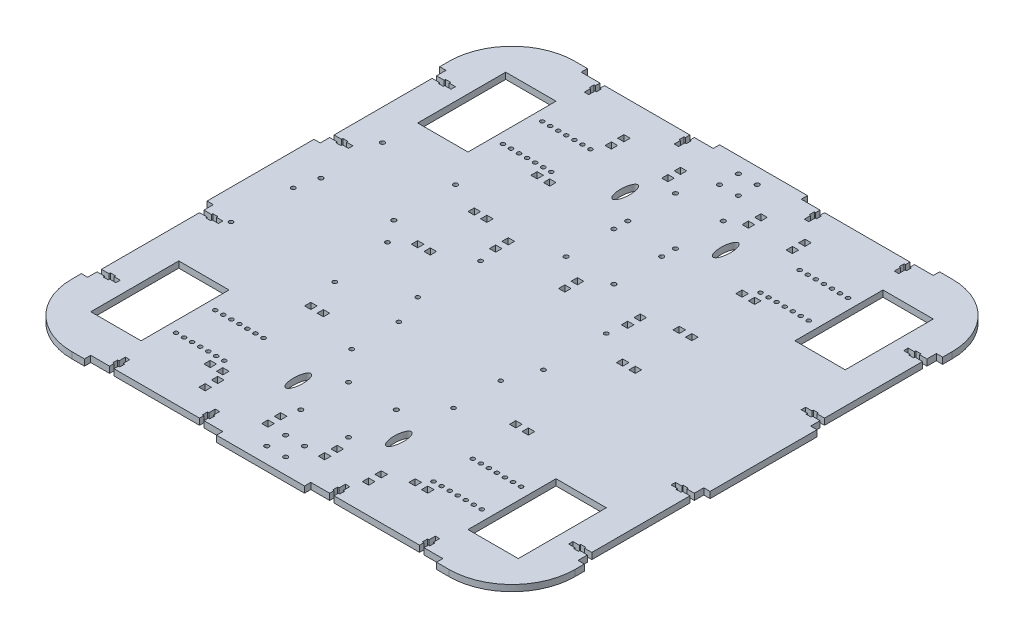
SolidWorks part; units mm, degrees
ref_plane "Front Plane" through (0, 0, 0) normal (0, 0, 1) x (1, 0, 0)
ref_plane "Top Plane" through (0, 0, 0) normal (0, 1, 0) x (1, 0, 0)
ref_plane "Right Plane" through (0, 0, 0) normal (1, 0, 0) x (0, 0, -1)
sketch "Sketch1" plane through (0, 0, 0) normal (0, 1, 0) x (1, 0, 0)
  line L0 (0, -1000) -> (0, 49000) construction
  line L1 (-170, 165) -> (-130, 165)
  line L2 (-170, 165) -> (-170, 95)
  line L3 (-170, 95) -> (-130, 95)
  line L4 (-130, 165) -> (-130, 95)
  line L5 (170, 95) -> (130, 95)
  line L6 (130, 165) -> (130, 95)
  line L7 (170, 165) -> (130, 165)
  line L8 (170, 165) -> (170, 95)
  line L9 (-1000, 0) -> (49000, 0) construction
  line L10 (-10, 190) -> (10, 190)
  line L11 (-10, 190) -> (-10, 170)
  line L12 (-10, 170) -> (10, 170)
  line L13 (10, 190) -> (10, 170)
  line L14 (-1010, 180) -> (48990, 180) construction
  line L15 (-1010, -180) -> (48990, -180) construction
  line L16 (0, 1000) -> (0, -49000) construction
  line L17 (-10, -170) -> (10, -170)
  line L18 (10, -190) -> (10, -170)
  line L19 (-10, -190) -> (10, -190)
  line L20 (-10, -190) -> (-10, -170)
  line L21 (170, -165) -> (170, -95)
  line L22 (-200, 200) -> (200, 200)
  line L23 (-200, 200) -> (-200, -200)
  line L24 (-200, -200) -> (200, -200)
  line L25 (200, 200) -> (200, -200)
  line L26 (170, -165) -> (130, -165)
  line L27 (130, -165) -> (130, -95)
  line L28 (170, -95) -> (130, -95)
  line L29 (-170, -95) -> (-130, -95)
  line L30 (-130, -165) -> (-130, -95)
  line L31 (-170, -165) -> (-130, -165)
  line L32 (-170, -165) -> (-170, -95)
  circle A0 centre (0, 0) radius 200 construction
  circle A1 centre (-7.5, 187.5) radius 1.75
  circle A2 centre (7.5, 187.5) radius 1.75
  circle A3 centre (7.5, 172.5) radius 1.75
  circle A4 centre (-7.5, 172.5) radius 1.75
  circle A5 centre (7.5, -187.5) radius 1.75
  circle A6 centre (-7.5, -187.5) radius 1.75
  circle A7 centre (-7.5, -172.5) radius 1.75
  circle A8 centre (7.5, -172.5) radius 1.75
  point P8 (-150, 165)
  point P19 (0, 190)
  point P22 (-10, 180)
  dimension "D1" = 400
  dimension "D7" = 3.5
  dimension "D2" = 40
  dimension "D3" = 70
  dimension "D4" = 150
  dimension "D5" = 20
  dimension "D6" = 180
  dimension "D8" = 2.5
  dimension "D9" = 2.5
  dimension "D10" = 35
extrude "Boss-Extrude2" add sketch "Sketch1" along normal blind 5 contours L25 L22 L23 L24 L1 L4 L3 L2 L7 L8 L5 L6 L10 L13 L12 L11 L19 L20 L17 L18 | L20 L19 L18 L17 A6 A5 A7 A8 | L13 L10 L11 L12 A2 A1 A3 A4 region at (0, 0, -180) region at (0, 0, 180) region at (0, 0, 0)
fillet "Fillet1" radius 50 4 edges at (200, 2.5, -200) (200, 2.5, 200) (-200, 2.5, 200) (-200, 2.5, -200)
sketch "Sketch2" plane through (0, 5, 0) normal (0, 1, 0) x (1, 0, 0)
  line L0 (-1094.0419, 130) -> (48905.9581, 130) construction
  line L1 (-130, 148.8) -> (-78.5, 148.8) construction
  line L2 (-130, 148.8) -> (-130, 111.2) construction
  line L3 (-130, 111.2) -> (-78.5, 111.2) construction
  line L4 (-78.5, 148.8) -> (-78.5, 111.2) construction
  line L5 (-130, 165) -> (-130, 95) construction
  line L6 (-170, 165) -> (-170, 95) construction
  line L7 (0, -1000) -> (0, 49000) construction
  line L8 (130, 111.2) -> (78.5, 111.2) construction
  line L9 (78.5, 148.8) -> (78.5, 111.2) construction
  line L10 (130, 148.8) -> (78.5, 148.8) construction
  line L11 (130, 148.8) -> (130, 111.2) construction
  line L12 (-1000, 0) -> (49000, 0) construction
  line L13 (130, -148.8) -> (130, -111.2) construction
  line L14 (130, -148.8) -> (78.5, -148.8) construction
  line L15 (78.5, -148.8) -> (78.5, -111.2) construction
  line L16 (130, -111.2) -> (78.5, -111.2) construction
  line L17 (-78.5, -148.8) -> (-78.5, -111.2) construction
  line L18 (-130, -111.2) -> (-78.5, -111.2) construction
  line L19 (-130, -148.8) -> (-130, -111.2) construction
  line L20 (-130, -148.8) -> (-78.5, -148.8) construction
  line L21 (-1094.0419, -130) -> (48905.9581, -130) construction
  circle A0 centre (-121.6, 145.6) radius 1.6
  circle A1 centre (-115.2, 145.6) radius 1.6
  circle A2 centre (-108.8, 145.6) radius 1.6
  circle A3 centre (-102.4, 145.6) radius 1.6
  circle A4 centre (-96, 145.6) radius 1.6
  circle A5 centre (-89.6, 145.6) radius 1.6
  circle A6 centre (-83.2, 145.6) radius 1.6
  circle A7 centre (-83.2, 114.4) radius 1.6
  circle A8 centre (-89.6, 114.4) radius 1.6
  circle A9 centre (-96, 114.4) radius 1.6
  circle A10 centre (-102.4, 114.4) radius 1.6
  circle A11 centre (-108.8, 114.4) radius 1.6
  circle A12 centre (-115.2, 114.4) radius 1.6
  circle A13 centre (-121.6, 114.4) radius 1.6
  circle A14 centre (83.2, 114.4) radius 1.6
  circle A15 centre (89.6, 114.4) radius 1.6
  circle A16 centre (96, 114.4) radius 1.6
  circle A17 centre (102.4, 114.4) radius 1.6
  circle A18 centre (108.8, 114.4) radius 1.6
  circle A19 centre (115.2, 114.4) radius 1.6
  circle A20 centre (121.6, 114.4) radius 1.6
  circle A21 centre (83.2, 145.6) radius 1.6
  circle A22 centre (89.6, 145.6) radius 1.6
  circle A23 centre (96, 145.6) radius 1.6
  circle A24 centre (102.4, 145.6) radius 1.6
  circle A25 centre (108.8, 145.6) radius 1.6
  circle A26 centre (115.2, 145.6) radius 1.6
  circle A27 centre (121.6, 145.6) radius 1.6
  circle A28 centre (121.6, -145.6) radius 1.6
  circle A29 centre (115.2, -145.6) radius 1.6
  circle A30 centre (108.8, -145.6) radius 1.6
  circle A31 centre (102.4, -145.6) radius 1.6
  circle A32 centre (96, -145.6) radius 1.6
  circle A33 centre (89.6, -145.6) radius 1.6
  circle A34 centre (83.2, -145.6) radius 1.6
  circle A35 centre (121.6, -114.4) radius 1.6
  circle A36 centre (115.2, -114.4) radius 1.6
  circle A37 centre (108.8, -114.4) radius 1.6
  circle A38 centre (102.4, -114.4) radius 1.6
  circle A39 centre (96, -114.4) radius 1.6
  circle A40 centre (89.6, -114.4) radius 1.6
  circle A41 centre (83.2, -114.4) radius 1.6
  circle A42 centre (-121.6, -114.4) radius 1.6
  circle A43 centre (-115.2, -114.4) radius 1.6
  circle A44 centre (-108.8, -114.4) radius 1.6
  circle A45 centre (-102.4, -114.4) radius 1.6
  circle A46 centre (-96, -114.4) radius 1.6
  circle A47 centre (-89.6, -114.4) radius 1.6
  circle A48 centre (-83.2, -114.4) radius 1.6
  circle A49 centre (-83.2, -145.6) radius 1.6
  circle A50 centre (-89.6, -145.6) radius 1.6
  circle A51 centre (-96, -145.6) radius 1.6
  circle A52 centre (-102.4, -145.6) radius 1.6
  circle A53 centre (-108.8, -145.6) radius 1.6
  circle A54 centre (-115.2, -145.6) radius 1.6
  circle A55 centre (-121.6, -145.6) radius 1.6
  point P9 (-130, 130)
  point P40 (-170, 130)
  dimension "D3" = 3.2
  dimension "D7" = 6.4
  dimension "D5" = 8.4
  dimension "D1" = 37.6
  dimension "D2" = 4.7
  dimension "D4" = 31.2
  dimension "D6" = 7
extrude "Cut-Extrude1" cut sketch "Sketch2" against normal blind 5
sketch "Sketch3" plane through (0, 5, 0) normal (0, 1, 0) x (1, 0, 0)
  line L0 (-150, -200) -> (150, -200) construction
  line L1 (-190, 3.34) -> (-88.4, 3.34) construction
  line L2 (-190, 3.34) -> (-190, -50) construction
  line L3 (-190, -50) -> (-88.4, -50) construction
  line L4 (-88.4, 3.34) -> (-88.4, -50) construction
  line L5 (-200, 150) -> (-200, -150) construction
  circle A0 centre (-176.03, -47.46) radius 1.65
  circle A1 centre (-174.76, 0.8) radius 1.65
  circle A2 centre (-93.48, -47.46) radius 1.65
  circle A3 centre (-99.83, 0.8) radius 1.65
  dimension "D5" = 3.3
  dimension "D8" = 3.3
  dimension "D9" = 96.52
  dimension "D10" = 90.17
  dimension "D1" = 101.6
  dimension "D2" = 53.34
  dimension "D3" = 13.97
  dimension "D4" = 2.54
  dimension "D6" = 15.24
  dimension "D7" = 50.8
  dimension "D11" = 150
  dimension "D12" = 10
extrude "Cut-Extrude2" cut sketch "Sketch3" against normal blind 10 contours A1 | A2 | L2 L1 L4 L3 | A0 | A3 region at (-174.76, 5, -0.8) region at (-93.48, 5, 47.46)
sketch "Sketch4" plane through (0, 5, 0) normal (0, 1, 0) x (1, 0, 0)
  line L0 (-19, 149) -> (19, 149) construction
  line L1 (-1149.7342, 130) -> (48850.2658, 130) construction
  line L2 (-22, 152) -> (22, 152) construction
  line L3 (-22, 152) -> (-22, 108) construction
  line L4 (-22, 108) -> (22, 108) construction
  line L5 (22, 152) -> (22, 108) construction
  line L6 (-19, 111) -> (19, 111) construction
  line L7 (-19, 100) -> (19, 100) construction
  line L8 (-1231.3219, 81) -> (48768.6781, 81) construction
  line L9 (-22, 103) -> (22, 103) construction
  line L10 (-22, 103) -> (-22, 59) construction
  line L11 (-22, 59) -> (22, 59) construction
  line L12 (22, 103) -> (22, 59) construction
  line L13 (-19, 62) -> (19, 62) construction
  line L14 (-19, -149) -> (19, -149) construction
  line L15 (-22, -152) -> (22, -152) construction
  line L16 (-130, 165) -> (-130, 95) construction
  line L17 (-150, 200) -> (150, 200) construction
  line L18 (22, -108) -> (22, -152) construction
  line L19 (-22, -108) -> (-22, -152) construction
  line L20 (-19, -111) -> (19, -111) construction
  line L21 (-22, -108) -> (22, -108) construction
  line L22 (-1022, -130) -> (48978, -130) construction
  line L23 (-130, -165) -> (-130, -95) construction
  circle A0 centre (-19, 149) radius 1.75
  circle A1 centre (19, 149) radius 1.75
  circle A2 centre (19, 111) radius 1.75
  circle A3 centre (-19, 111) radius 1.75
  circle A4 centre (-19, 100) radius 1.75
  circle A5 centre (19, 100) radius 1.75
  circle A6 centre (19, 62) radius 1.75
  circle A7 centre (-19, 62) radius 1.75
  circle A8 centre (-19, -149) radius 1.75
  circle A9 centre (19, -149) radius 1.75
  circle A10 centre (-19, -111) radius 1.75
  circle A11 centre (19, -111) radius 1.75
  point P9 (0, 149)
  point P10 (0, 152)
  point P14 (-22, 130)
  point P26 (0, 100)
  point P27 (0, 103)
  point P31 (-22, 81)
  point P38 (-130, 130)
  point P39 (0, 200)
  point P40 (0, 108)
  point P56 (-22, -130)
  point P58 (-130, -130)
  dimension "D1" = 3.5
  dimension "D5" = 3.5
  dimension "D2" = 38
  dimension "D3" = 44
  dimension "D4" = 38
  dimension "D6" = 38
  dimension "D7" = 44
  dimension "D8" = 38
  dimension "D9" = 5
  dimension "D10" = 2
extrude "Cut-Extrude3" cut sketch "Sketch4" against normal blind 10
sketch "Sketch5" plane through (0, 5, 0) normal (0, 1, 0) x (1, 0, 0)
  line L0 (-1136.3236, 43) -> (48863.6764, 43) construction
  line L1 (-174, 15) -> (-89, 15) construction
  line L2 (-174, 15) -> (-174, 71) construction
  line L3 (-174, 71) -> (-89, 71) construction
  line L4 (-89, 15) -> (-89, 71) construction
  line L5 (-180, 10) -> (-83, 10) construction
  line L6 (-180, 10) -> (-180, 76) construction
  line L7 (-180, 76) -> (-83, 76) construction
  line L8 (-83, 10) -> (-83, 76) construction
  line L9 (-200, 150) -> (-200, -150) construction
  line L10 (-150, -200) -> (150, -200) construction
  circle A0 centre (-170.5, 67.5) radius 1.75
  circle A1 centre (-112.5, 67.5) radius 1.75
  circle A2 centre (-112.5, 18.5) radius 1.75
  circle A3 centre (-170.5, 18.5) radius 1.75
  dimension "D4" = 3.5
  dimension "D5" = 3.5
  dimension "D1" = 56
  dimension "D2" = 85
  dimension "D3" = 58
  dimension "D6" = 3.5
  dimension "D7" = 49
  dimension "D8" = 3.5
  dimension "D9" = 5
  dimension "D10" = 5
  dimension "D11" = 6
  dimension "D12" = 6
  dimension "D13" = 20
  dimension "D14" = 210
extrude "Cut-Extrude4" cut sketch "Sketch5" against normal blind 10
sketch "Sketch6" plane through (0, 5, 0) normal (0, 1, 0) x (1, 0, 0)
  line L0 (-130, 165) -> (-130, 95) construction
  line L1 (0, -800) -> (0, 49200) construction
  line L2 (-150, 200) -> (150, 200) construction
  line L3 (-1200, 0) -> (48800, 0) construction
  line L4 (-200, 150) -> (-200, -150) construction
  ellipse E0 centre (-40, 130) end of major axis (-40, 140) minor radius 3.75
  ellipse E1 centre (40, 130) end of major axis (40, 140) minor radius 3.75
  ellipse E2 centre (40, -130) end of major axis (40, -140) minor radius 3.75
  ellipse E3 centre (-40, -130) end of major axis (-40, -140) minor radius 3.75
  point P13 (-130, 130)
  point P14 (-200, 0)
  point P26 (0, 200)
  dimension "D1" = 90
  dimension "D2" = 20
  dimension "D3" = 7.5
extrude "Cut-Extrude5" cut sketch "Sketch6" against normal blind 10
sketch "Sketch7" plane through (0, 5, 0) normal (0, 1, 0) x (1, 0, 0)
  line L0 (0, -1008.1082) -> (0, 48991.8918) construction
  line L1 (-53, 28) -> (53, 28) construction
  line L2 (-53, 28) -> (-53, -28) construction
  line L3 (-53, -28) -> (53, -28) construction
  line L4 (53, 28) -> (53, -28) construction
  line L5 (-53, 28) -> (-47, 28) construction
  line L6 (-53, 28) -> (-53, 22) construction
  line L7 (-53, 22) -> (-47, 22) construction
  line L8 (-47, 28) -> (-47, 22) construction
  line L9 (-1053, 0) -> (48947, 0) construction
  line L10 (-150, -200) -> (150, -200) construction
  line L11 (-200, 150) -> (-200, -150) construction
  circle A1 centre (-50, 25) radius 1.65
  circle A2 centre (50, 25) radius 1.65
  circle A3 centre (50, -25) radius 1.65
  circle A4 centre (-50, -25) radius 1.65
  point P10 (-50, 22)
  point P15 (-47, 25)
  point P16 (0, 28)
  point P17 (-53, 0)
  point P25 (0, -200)
  point P28 (-200, 0)
  dimension "D3" = 3.3
  dimension "D1" = 106
  dimension "D2" = 56
  dimension "D5" = 6
  dimension "D6" = 6
extrude "Cut-Extrude6" cut sketch "Sketch7" against normal blind 10
sketch "Sketch8" plane through (0, 5, 0) normal (0, 1, 0) x (1, 0, 0)
  line L0 (0, -1046.6714) -> (0, 48953.3286) construction
  line L1 (-43.5, -46.5) -> (43.5, -46.5) construction
  line L2 (-43.5, -46.5) -> (-43.5, -90) construction
  line L3 (-43.5, -90) -> (43.5, -90) construction
  line L4 (43.5, -46.5) -> (43.5, -90) construction
  line L5 (-43.5, -46.5) -> (-37.5, -46.5) construction
  line L6 (-43.5, -46.5) -> (-43.5, -52.5) construction
  line L7 (-43.5, -52.5) -> (-37.5, -52.5) construction
  line L8 (-37.5, -46.5) -> (-37.5, -52.5) construction
  line L9 (-1043.5, -68.25) -> (48956.5, -68.25) construction
  line L10 (37.5, -46.5) -> (37.5, -52.5) construction
  line L11 (43.5, -52.5) -> (37.5, -52.5) construction
  line L12 (-150, -200) -> (150, -200) construction
  circle A0 centre (-40.5, -49.5) radius 1.65
  circle A1 centre (40.5, -49.5) radius 1.65
  circle A2 centre (40.5, -87) radius 1.65
  circle A3 centre (-40.5, -87) radius 1.65
  point P10 (-40.5, -52.5)
  point P11 (-37.5, -49.5)
  point P15 (0, -46.5)
  point P17 (-43.5, -68.25)
  point P28 (0, -200)
  dimension "D3" = 3.3
  dimension "D1" = 87
  dimension "D2" = 6
  dimension "D4" = 43.5
  dimension "D5" = 110
extrude "Cut-Extrude7" cut sketch "Sketch8" against normal blind 5
sketch "Sketch10" plane through (0, 5, 0) normal (0, 1, 0) x (1, 0, 0)
  line L0 (-150, -200) -> (150, -200) construction
  line L1 (-125, -200) -> (-121.5, -200)
  line L2 (-125, -200) -> (-125, -191.5)
  line L3 (-125, -182.5) -> (-121.5, -182.5)
  line L4 (-121.5, -200) -> (-121.5, -191.5)
  line L6 (-121.5, -187.5) -> (-120.4, -187.5)
  line L7 (-126.1, -187.5) -> (-125, -187.5)
  line L8 (-126.1, -187.5) -> (-126.1, -191.5)
  line L9 (-126.1, -191.5) -> (-125, -191.5)
  line L10 (-120.4, -187.5) -> (-120.4, -191.5)
  line L11 (-121.5, -191.5) -> (-120.4, -191.5)
  line L12 (-125, -187.5) -> (-125, -182.5)
  line L13 (-121.5, -187.5) -> (-121.5, -182.5)
  line L14 (-125, -187.5) -> (-121.5, -187.5) construction
  line L15 (-121.5, -191.5) -> (-125, -191.5) construction
  line L16 (-53.5, -200) -> (-50, -200)
  line L17 (-50, -200) -> (-50, -191.5)
  line L18 (-50, -191.5) -> (-48.9, -191.5)
  line L19 (-48.9, -187.5) -> (-48.9, -191.5)
  line L20 (-50, -187.5) -> (-48.9, -187.5)
  line L21 (-50, -187.5) -> (-50, -182.5)
  line L22 (-53.5, -182.5) -> (-50, -182.5)
  line L23 (-53.5, -187.5) -> (-53.5, -182.5)
  line L24 (-54.6, -187.5) -> (-53.5, -187.5)
  line L25 (-54.6, -187.5) -> (-54.6, -191.5)
  line L26 (-54.6, -191.5) -> (-53.5, -191.5)
  line L27 (-53.5, -200) -> (-53.5, -191.5)
  line L28 (-50, -191.5) -> (-53.5, -191.5) construction
  line L29 (-53.5, -187.5) -> (-50, -187.5) construction
  line L30 (0, -1200) -> (0, 48800) construction
  line L31 (-200, 150) -> (-200, -150) construction
  line L32 (121.5, -191.5) -> (125, -191.5) construction
  line L33 (125, -187.5) -> (121.5, -187.5) construction
  line L34 (125, -200) -> (125, -191.5)
  line L35 (126.1, -191.5) -> (125, -191.5)
  line L36 (126.1, -187.5) -> (126.1, -191.5)
  line L37 (126.1, -187.5) -> (125, -187.5)
  line L38 (125, -187.5) -> (125, -182.5)
  line L39 (125, -182.5) -> (121.5, -182.5)
  line L40 (121.5, -187.5) -> (121.5, -182.5)
  line L41 (121.5, -187.5) -> (120.4, -187.5)
  line L42 (120.4, -187.5) -> (120.4, -191.5)
  line L43 (121.5, -191.5) -> (120.4, -191.5)
  line L44 (121.5, -200) -> (121.5, -191.5)
  line L45 (125, -200) -> (121.5, -200)
  line L46 (53.5, -187.5) -> (50, -187.5) construction
  line L47 (50, -191.5) -> (53.5, -191.5) construction
  line L48 (53.5, -200) -> (53.5, -191.5)
  line L49 (54.6, -191.5) -> (53.5, -191.5)
  line L50 (54.6, -187.5) -> (54.6, -191.5)
  line L51 (54.6, -187.5) -> (53.5, -187.5)
  line L52 (53.5, -187.5) -> (53.5, -182.5)
  line L53 (53.5, -182.5) -> (50, -182.5)
  line L54 (50, -187.5) -> (50, -182.5)
  line L55 (50, -187.5) -> (48.9, -187.5)
  line L56 (48.9, -187.5) -> (48.9, -191.5)
  line L57 (50, -191.5) -> (48.9, -191.5)
  line L58 (50, -200) -> (50, -191.5)
  line L59 (53.5, -200) -> (50, -200)
  line L60 (-1000, 0) -> (49000, 0) construction
  line L61 (125, 200) -> (121.5, 200)
  line L62 (121.5, 200) -> (121.5, 191.5)
  line L63 (121.5, 191.5) -> (120.4, 191.5)
  line L64 (120.4, 187.5) -> (120.4, 191.5)
  line L65 (121.5, 187.5) -> (120.4, 187.5)
  line L66 (121.5, 187.5) -> (121.5, 182.5)
  line L67 (125, 182.5) -> (121.5, 182.5)
  line L68 (125, 187.5) -> (125, 182.5)
  line L69 (126.1, 187.5) -> (125, 187.5)
  line L70 (126.1, 187.5) -> (126.1, 191.5)
  line L71 (126.1, 191.5) -> (125, 191.5)
  line L72 (125, 200) -> (125, 191.5)
  line L73 (53.5, 200) -> (50, 200)
  line L74 (50, 200) -> (50, 191.5)
  line L75 (50, 191.5) -> (48.9, 191.5)
  line L76 (48.9, 187.5) -> (48.9, 191.5)
  line L77 (50, 187.5) -> (48.9, 187.5)
  line L78 (50, 187.5) -> (50, 182.5)
  line L79 (53.5, 182.5) -> (50, 182.5)
  line L80 (53.5, 187.5) -> (53.5, 182.5)
  line L81 (54.6, 187.5) -> (53.5, 187.5)
  line L82 (54.6, 187.5) -> (54.6, 191.5)
  line L83 (54.6, 191.5) -> (53.5, 191.5)
  line L84 (53.5, 200) -> (53.5, 191.5)
  line L85 (-53.5, 200) -> (-53.5, 191.5)
  line L86 (-54.6, 191.5) -> (-53.5, 191.5)
  line L87 (-54.6, 187.5) -> (-54.6, 191.5)
  line L88 (-54.6, 187.5) -> (-53.5, 187.5)
  line L89 (-53.5, 187.5) -> (-53.5, 182.5)
  line L90 (-53.5, 182.5) -> (-50, 182.5)
  line L91 (-50, 187.5) -> (-50, 182.5)
  line L92 (-50, 187.5) -> (-48.9, 187.5)
  line L93 (-48.9, 187.5) -> (-48.9, 191.5)
  line L94 (-50, 191.5) -> (-48.9, 191.5)
  line L95 (-50, 200) -> (-50, 191.5)
  line L96 (-53.5, 200) -> (-50, 200)
  line L97 (-125, 200) -> (-125, 191.5)
  line L98 (-126.1, 191.5) -> (-125, 191.5)
  line L99 (-126.1, 187.5) -> (-126.1, 191.5)
  line L100 (-126.1, 187.5) -> (-125, 187.5)
  line L101 (-125, 187.5) -> (-125, 182.5)
  line L102 (-125, 182.5) -> (-121.5, 182.5)
  line L103 (-121.5, 187.5) -> (-121.5, 182.5)
  line L104 (-121.5, 187.5) -> (-120.4, 187.5)
  line L105 (-120.4, 187.5) -> (-120.4, 191.5)
  line L106 (-121.5, 191.5) -> (-120.4, 191.5)
  line L107 (-121.5, 200) -> (-121.5, 191.5)
  line L108 (-125, 200) -> (-121.5, 200)
  point P11 (-123.25, -200)
  point P15 (-123.25, -191.5)
  point P16 (-123.25, -187.5)
  point P17 (-123.25, -182.5)
  point P33 (0, -200)
  dimension "D1" = 3.5
  dimension "D2" = 5.7
  dimension "D3" = 5
  dimension "D4" = 4
  dimension "D5" = 1.1
  dimension "D7" = 75
  dimension "D8" = 50
  dimension "D9" = 17.5
  dimension "D6" = 2
extrude "Cut-Extrude8" cut sketch "Sketch10" against normal blind 10
sketch "Sketch11" plane through (0, 5, 0) normal (0, 1, 0) x (1, 0, 0)
  line L0 (-150, -200) -> (-125, -200) construction
  line L1 (-140, -200) -> (-35, -200)
  line L2 (-140, -200) -> (-140, -195)
  line L3 (-140, -195) -> (-35, -195)
  line L4 (-35, -200) -> (-35, -195)
  line L5 (-50, -200) -> (-50, -191.5) construction
  line L6 (-125, -191.5) -> (-125, -200) construction
  line L7 (0, -1200) -> (0, 48800) construction
  line L8 (-50, -200) -> (50, -200) construction
  line L9 (-1200, 0) -> (48800, 0) construction
  line L10 (-200, 150) -> (-200, -150) construction
  line L11 (140, -195) -> (35, -195)
  line L12 (35, -200) -> (35, -195)
  line L13 (140, -200) -> (35, -200)
  line L14 (140, -200) -> (140, -195)
  line L15 (140, 200) -> (140, 195)
  line L16 (140, 200) -> (35, 200)
  line L17 (35, 200) -> (35, 195)
  line L18 (140, 195) -> (35, 195)
  line L19 (-140, 195) -> (-35, 195)
  line L20 (-35, 200) -> (-35, 195)
  line L21 (-140, 200) -> (-35, 200)
  line L22 (-140, 200) -> (-140, 195)
  point P15 (0, -200)
  point P20 (-200, 0)
  dimension "D1" = 5
  dimension "D2" = 15
  dimension "D3" = 15
extrude "Cut-Extrude9" cut sketch "Sketch11" against normal blind 10
sketch "Sketch12" plane through (0, 5, 0) normal (0, 1, 0) x (1, 0, 0)
  line L0 (-200, 150) -> (-200, -150) construction
  line L1 (-200, 135) -> (-189, 135)
  line L2 (-200, 135) -> (-200, 131.5)
  line L3 (-200, 131.5) -> (-189, 131.5)
  line L4 (-180, 135) -> (-180, 131.5)
  line L5 (-200, 53.5) -> (-189, 53.5)
  line L6 (-189, 131.5) -> (-189, 130.4)
  line L7 (-189, 136.1) -> (-185, 136.1)
  line L8 (-189, 136.1) -> (-189, 135)
  line L9 (-189, 130.4) -> (-185, 130.4)
  line L10 (-185, 136.1) -> (-185, 135)
  line L11 (-185, 131.5) -> (-185, 130.4)
  line L12 (-185, 135) -> (-180, 135)
  line L13 (-185, 131.5) -> (-180, 131.5)
  line L14 (-189, 135) -> (-189, 131.5) construction
  line L15 (-185, 131.5) -> (-185, 135) construction
  line L16 (-189, 54.6) -> (-189, 53.5)
  line L17 (-189, 54.6) -> (-185, 54.6)
  line L18 (-185, 54.6) -> (-185, 53.5)
  line L19 (-185, 53.5) -> (-180, 53.5)
  line L20 (-180, 53.5) -> (-180, 50)
  line L21 (-185, 50) -> (-180, 50)
  line L22 (-185, 50) -> (-185, 48.9)
  line L23 (-189, 48.9) -> (-185, 48.9)
  line L24 (-189, 50) -> (-189, 48.9)
  line L25 (-200, 50) -> (-189, 50)
  line L26 (-200, 53.5) -> (-200, 50)
  line L27 (-1200, 0) -> (48800, 0) construction
  line L28 (-200, -53.5) -> (-200, -50)
  line L29 (-200, -50) -> (-189, -50)
  line L30 (-189, -50) -> (-189, -48.9)
  line L31 (-189, -48.9) -> (-185, -48.9)
  line L32 (-185, -50) -> (-185, -48.9)
  line L33 (-185, -50) -> (-180, -50)
  line L34 (-180, -53.5) -> (-180, -50)
  line L35 (-185, -53.5) -> (-180, -53.5)
  line L36 (-185, -54.6) -> (-185, -53.5)
  line L37 (-189, -54.6) -> (-185, -54.6)
  line L38 (-189, -54.6) -> (-189, -53.5)
  line L39 (-200, -53.5) -> (-189, -53.5)
  line L40 (-200, -135) -> (-200, -131.5)
  line L41 (-200, -131.5) -> (-189, -131.5)
  line L42 (-189, -131.5) -> (-189, -130.4)
  line L43 (-189, -130.4) -> (-185, -130.4)
  line L44 (-185, -131.5) -> (-185, -130.4)
  line L45 (-185, -131.5) -> (-180, -131.5)
  line L46 (-180, -135) -> (-180, -131.5)
  line L47 (-185, -135) -> (-180, -135)
  line L48 (-185, -136.1) -> (-185, -135)
  line L49 (-189, -136.1) -> (-185, -136.1)
  line L50 (-189, -136.1) -> (-189, -135)
  line L51 (-200, -135) -> (-189, -135)
  line L52 (0, -1200) -> (0, 48800) construction
  line L53 (-35, -200) -> (35, -200) construction
  line L54 (200, -135) -> (189, -135)
  line L55 (189, -136.1) -> (189, -135)
  line L56 (189, -136.1) -> (185, -136.1)
  line L57 (185, -136.1) -> (185, -135)
  line L58 (185, -135) -> (180, -135)
  line L59 (180, -135) -> (180, -131.5)
  line L60 (185, -131.5) -> (180, -131.5)
  line L61 (185, -131.5) -> (185, -130.4)
  line L62 (189, -130.4) -> (185, -130.4)
  line L63 (189, -131.5) -> (189, -130.4)
  line L64 (200, -131.5) -> (189, -131.5)
  line L65 (200, -135) -> (200, -131.5)
  line L66 (200, -53.5) -> (189, -53.5)
  line L67 (189, -54.6) -> (189, -53.5)
  line L68 (189, -54.6) -> (185, -54.6)
  line L69 (185, -54.6) -> (185, -53.5)
  line L70 (185, -53.5) -> (180, -53.5)
  line L71 (180, -53.5) -> (180, -50)
  line L72 (185, -50) -> (180, -50)
  line L73 (185, -50) -> (185, -48.9)
  line L74 (189, -48.9) -> (185, -48.9)
  line L75 (189, -50) -> (189, -48.9)
  line L76 (200, -50) -> (189, -50)
  line L77 (200, -53.5) -> (200, -50)
  line L78 (200, 53.5) -> (200, 50)
  line L79 (200, 50) -> (189, 50)
  line L80 (189, 50) -> (189, 48.9)
  line L81 (189, 48.9) -> (185, 48.9)
  line L82 (185, 50) -> (185, 48.9)
  line L83 (185, 50) -> (180, 50)
  line L84 (180, 53.5) -> (180, 50)
  line L85 (185, 53.5) -> (180, 53.5)
  line L86 (185, 54.6) -> (185, 53.5)
  line L87 (189, 54.6) -> (185, 54.6)
  line L88 (189, 54.6) -> (189, 53.5)
  line L89 (200, 53.5) -> (189, 53.5)
  line L90 (200, 135) -> (200, 131.5)
  line L91 (200, 131.5) -> (189, 131.5)
  line L92 (189, 131.5) -> (189, 130.4)
  line L93 (189, 130.4) -> (185, 130.4)
  line L94 (185, 131.5) -> (185, 130.4)
  line L95 (185, 131.5) -> (180, 131.5)
  line L96 (180, 135) -> (180, 131.5)
  line L97 (185, 135) -> (180, 135)
  line L98 (185, 136.1) -> (185, 135)
  line L99 (189, 136.1) -> (185, 136.1)
  line L100 (189, 136.1) -> (189, 135)
  line L101 (200, 135) -> (189, 135)
  point P31 (-200, 0)
  point P60 (0, -200)
  dimension "D1" = 20
  dimension "D2" = 3.5
  dimension "D3" = 5.7
  dimension "D4" = 5
  dimension "D5" = 4
  dimension "D6" = 15
  dimension "D7" = 1.1
  dimension "D9" = 50
  dimension "D8" = 2
extrude "Cut-Extrude10" cut sketch "Sketch12" against normal blind 5
sketch "Sketch13" plane through (0, 5, 0) normal (0, 1, 0) x (1, 0, 0)
  line L0 (-200, 150) -> (-200, 135) construction
  line L1 (-200, 142.5) -> (-195, 142.5)
  line L2 (-200, 142.5) -> (-200, 42.5)
  line L3 (-200, 42.5) -> (-195, 42.5)
  line L4 (-195, 142.5) -> (-195, 42.5)
  line L6 (-200, 50) -> (-189, 50) construction
  line L7 (-1200, 0) -> (48800, 0) construction
  line L8 (-200, 50) -> (-200, -50) construction
  line L9 (0, -800) -> (0, 49200) construction
  line L10 (-35, 200) -> (35, 200) construction
  line L11 (-200, -42.5) -> (-195, -42.5)
  line L12 (-195, -142.5) -> (-195, -42.5)
  line L13 (-200, -142.5) -> (-195, -142.5)
  line L14 (-200, -142.5) -> (-200, -42.5)
  line L15 (0, 800) -> (0, -49200) construction
  line L16 (200, -142.5) -> (200, -42.5)
  line L17 (200, -142.5) -> (195, -142.5)
  line L18 (195, -142.5) -> (195, -42.5)
  line L19 (200, -42.5) -> (195, -42.5)
  line L20 (200, 42.5) -> (195, 42.5)
  line L21 (195, 142.5) -> (195, 42.5)
  line L22 (200, 142.5) -> (195, 142.5)
  line L23 (200, 142.5) -> (200, 42.5)
  point P13 (-200, 0)
  point P18 (0, 200)
  dimension "D1" = 7.5
  dimension "D2" = 5
extrude "Cut-Extrude11" cut sketch "Sketch13" against normal blind 5
sketch "Sketch14" plane through (0, 5, 0) normal (0, 1, 0) x (1, 0, 0)
  line L0 (34, 164) -> (29, 164)
  line L1 (34, 154) -> (29, 154)
  line L2 (34, 154) -> (34, 159)
  line L3 (34, 159) -> (29, 159)
  line L4 (29, 154) -> (29, 159)
  line L5 (34, 164) -> (34, 169)
  line L6 (34, 169) -> (29, 169)
  line L7 (29, 164) -> (29, 169)
  line L8 (69, 164) -> (64, 164)
  line L9 (69, 154) -> (64, 154)
  line L10 (69, 154) -> (69, 159)
  line L11 (69, 159) -> (64, 159)
  line L12 (64, 154) -> (64, 159)
  line L13 (69, 164) -> (69, 169)
  line L14 (69, 169) -> (64, 169)
  line L15 (64, 164) -> (64, 169)
  line L16 (5, 47) -> (0, 47)
  line L17 (5, 37) -> (0, 37)
  line L18 (5, 37) -> (5, 42)
  line L19 (5, 42) -> (0, 42)
  line L20 (0, 37) -> (0, 42)
  line L21 (5, 47) -> (5, 52)
  line L22 (5, 52) -> (0, 52)
  line L23 (0, 47) -> (0, 52)
  line L24 (55, 47) -> (50, 47)
  line L25 (55, 37) -> (50, 37)
  line L26 (55, 37) -> (55, 42)
  line L27 (55, 42) -> (50, 42)
  line L28 (50, 37) -> (50, 42)
  line L29 (55, 47) -> (55, 52)
  line L30 (55, 52) -> (50, 52)
  line L31 (50, 47) -> (50, 52)
  line L32 (25, -164) -> (20, -164)
  line L33 (25, -174) -> (20, -174)
  line L34 (25, -174) -> (25, -169)
  line L35 (25, -169) -> (20, -169)
  line L36 (20, -174) -> (20, -169)
  line L37 (25, -164) -> (25, -159)
  line L38 (25, -159) -> (20, -159)
  line L39 (20, -164) -> (20, -159)
  line L40 (60, -164) -> (55, -164)
  line L41 (60, -174) -> (55, -174)
  line L42 (60, -174) -> (60, -169)
  line L43 (60, -169) -> (55, -169)
  line L44 (55, -174) -> (55, -169)
  line L45 (60, -164) -> (60, -159)
  line L46 (60, -159) -> (55, -159)
  line L47 (55, -164) -> (55, -159)
  line L48 (-30, 164) -> (-35, 164)
  line L49 (-30, 154) -> (-35, 154)
  line L50 (-30, 154) -> (-30, 159)
  line L51 (-30, 159) -> (-35, 159)
  line L52 (-35, 154) -> (-35, 159)
  line L53 (-30, 164) -> (-30, 169)
  line L54 (-30, 169) -> (-35, 169)
  line L55 (-35, 164) -> (-35, 169)
  line L56 (-50, 47) -> (-55, 47)
  line L57 (-50, 37) -> (-55, 37)
  line L58 (-50, 37) -> (-50, 42)
  line L59 (-50, 42) -> (-55, 42)
  line L60 (-55, 37) -> (-55, 42)
  line L61 (-50, 47) -> (-50, 52)
  line L62 (-50, 52) -> (-55, 52)
  line L63 (-55, 47) -> (-55, 52)
  line L64 (-20, -164) -> (-25, -164)
  line L65 (-20, -174) -> (-25, -174)
  line L66 (-20, -174) -> (-20, -169)
  line L67 (-20, -169) -> (-25, -169)
  line L68 (-25, -174) -> (-25, -169)
  line L69 (-20, -164) -> (-20, -159)
  line L70 (-20, -159) -> (-25, -159)
  line L71 (-25, -164) -> (-25, -159)
  line L72 (19, 62) -> (-19, 62) construction
  line L73 (19, 149) -> (-19, 149) construction
  line L74 (-75, 164) -> (-80, 164)
  line L75 (-75, 154) -> (-80, 154)
  line L76 (-75, 154) -> (-75, 159)
  line L77 (-75, 159) -> (-80, 159)
  line L78 (-80, 154) -> (-80, 159)
  line L79 (-75, 164) -> (-75, 169)
  line L80 (-75, 169) -> (-80, 169)
  line L81 (-80, 164) -> (-80, 169)
  line L82 (19, -149) -> (-19, -149) construction
  line L83 (-70, -164) -> (-75, -164)
  line L84 (-70, -174) -> (-75, -174)
  line L85 (-70, -174) -> (-70, -169)
  line L86 (-70, -169) -> (-75, -169)
  line L87 (-75, -174) -> (-75, -169)
  line L88 (-70, -164) -> (-70, -159)
  line L89 (-70, -159) -> (-75, -159)
  line L90 (-75, -164) -> (-75, -159)
  line L91 (79, -156) -> (74, -156)
  line L92 (89, -156) -> (84, -156)
  line L93 (89, -156) -> (89, -151)
  line L94 (89, -151) -> (84, -151)
  line L95 (84, -156) -> (84, -151)
  line L96 (79, -156) -> (79, -151)
  line L97 (79, -151) -> (74, -151)
  line L98 (74, -156) -> (74, -151)
  line L99 (79, -76) -> (74, -76)
  line L100 (89, -76) -> (84, -76)
  line L101 (89, -76) -> (89, -71)
  line L102 (89, -71) -> (84, -71)
  line L103 (84, -76) -> (84, -71)
  line L104 (79, -76) -> (79, -71)
  line L105 (79, -71) -> (74, -71)
  line L106 (74, -76) -> (74, -71)
  line L107 (79, 9) -> (74, 9)
  line L108 (89, 9) -> (84, 9)
  line L109 (89, 9) -> (89, 14)
  line L110 (89, 14) -> (84, 14)
  line L111 (84, 9) -> (84, 14)
  line L112 (79, 9) -> (79, 14)
  line L113 (79, 14) -> (74, 14)
  line L114 (74, 9) -> (74, 14)
  line L115 (79, 54) -> (74, 54)
  line L116 (89, 54) -> (84, 54)
  line L117 (89, 54) -> (89, 59)
  line L118 (89, 59) -> (84, 59)
  line L119 (84, 54) -> (84, 59)
  line L120 (79, 54) -> (79, 59)
  line L121 (79, 59) -> (74, 59)
  line L122 (74, 54) -> (74, 59)
  line L123 (79, 104) -> (74, 104)
  line L124 (89, 104) -> (84, 104)
  line L125 (89, 104) -> (89, 109)
  line L126 (89, 109) -> (84, 109)
  line L127 (84, 104) -> (84, 109)
  line L128 (79, 104) -> (79, 109)
  line L129 (79, 109) -> (74, 109)
  line L130 (74, 104) -> (74, 109)
  line L131 (0, -1200) -> (0, 48800) construction
  line L132 (-35, -200) -> (35, -200) construction
  line L133 (-79, 104) -> (-79, 109)
  line L134 (-79, 109) -> (-74, 109)
  line L135 (-74, 104) -> (-74, 109)
  line L136 (-79, 104) -> (-74, 104)
  line L137 (-89, 104) -> (-89, 109)
  line L138 (-89, 109) -> (-84, 109)
  line L139 (-84, 104) -> (-84, 109)
  line L140 (-89, 104) -> (-84, 104)
  line L141 (-79, 54) -> (-79, 59)
  line L142 (-79, 59) -> (-74, 59)
  line L143 (-74, 54) -> (-74, 59)
  line L144 (-79, 54) -> (-74, 54)
  line L145 (-89, 54) -> (-89, 59)
  line L146 (-89, 59) -> (-84, 59)
  line L147 (-84, 54) -> (-84, 59)
  line L148 (-89, 54) -> (-84, 54)
  line L149 (-79, 9) -> (-79, 14)
  line L150 (-79, 14) -> (-74, 14)
  line L151 (-74, 9) -> (-74, 14)
  line L152 (-79, 9) -> (-74, 9)
  line L153 (-89, 9) -> (-89, 14)
  line L154 (-89, 14) -> (-84, 14)
  line L155 (-84, 9) -> (-84, 14)
  line L156 (-89, 9) -> (-84, 9)
  line L157 (-79, -76) -> (-79, -71)
  line L158 (-79, -71) -> (-74, -71)
  line L159 (-74, -76) -> (-74, -71)
  line L160 (-79, -76) -> (-74, -76)
  line L161 (-89, -76) -> (-89, -71)
  line L162 (-89, -71) -> (-84, -71)
  line L163 (-84, -76) -> (-84, -71)
  line L164 (-89, -76) -> (-84, -76)
  line L165 (-79, -156) -> (-79, -151)
  line L166 (-79, -151) -> (-74, -151)
  line L167 (-74, -156) -> (-74, -151)
  line L168 (-79, -156) -> (-74, -156)
  line L169 (-89, -156) -> (-89, -151)
  line L170 (-89, -151) -> (-84, -151)
  line L171 (-84, -156) -> (-84, -151)
  line L172 (-89, -156) -> (-84, -156)
  circle A0 centre (19, 149) radius 1.75 construction
  point P78 (0, 49.5)
  point P79 (0, 62)
  point P83 (0, 149)
  point P84 (0, -149)
  point P151 (0, -200)
  dimension "D20" = 10
  dimension "D1" = 5
  dimension "D2" = 5
  dimension "D3" = 5
  dimension "D4" = 5
  dimension "D5" = 5
  dimension "D6" = 5
  dimension "D7" = 5
  dimension "D8" = 5
  dimension "D9" = 5
  dimension "D10" = 5
  dimension "D11" = 5
  dimension "D12" = 5
  dimension "D13" = 5
  dimension "D14" = 5
  dimension "D15" = 5
  dimension "D16" = 5
  dimension "D17" = 5
  dimension "D18" = 5
  dimension "D19" = 30
  dimension "D21" = 10
  dimension "D22" = 10
  dimension "D23" = 45
  dimension "D24" = 50
  dimension "D25" = 30
  dimension "D26" = 5
  dimension "D27" = 5
  dimension "D28" = 40
  dimension "D29" = 20
  dimension "D30" = 10
  dimension "D31" = 30
  dimension "D32" = 20
  dimension "D33" = 5
  dimension "D34" = 5
  dimension "D35" = 45
  dimension "D36" = 5
  dimension "D37" = 5
  dimension "D38" = 5
  dimension "D39" = 5
  dimension "D40" = 5
  dimension "D41" = 5
  dimension "D42" = 5
  dimension "D43" = 5
  dimension "D44" = 5
  dimension "D45" = 5
  dimension "D46" = 5
  dimension "D47" = 45
  dimension "D48" = 45
  dimension "D49" = 40
  dimension "D50" = 80
  dimension "D51" = 75
extrude "Cut-Extrude12" cut sketch "Sketch14" against normal blind 10
